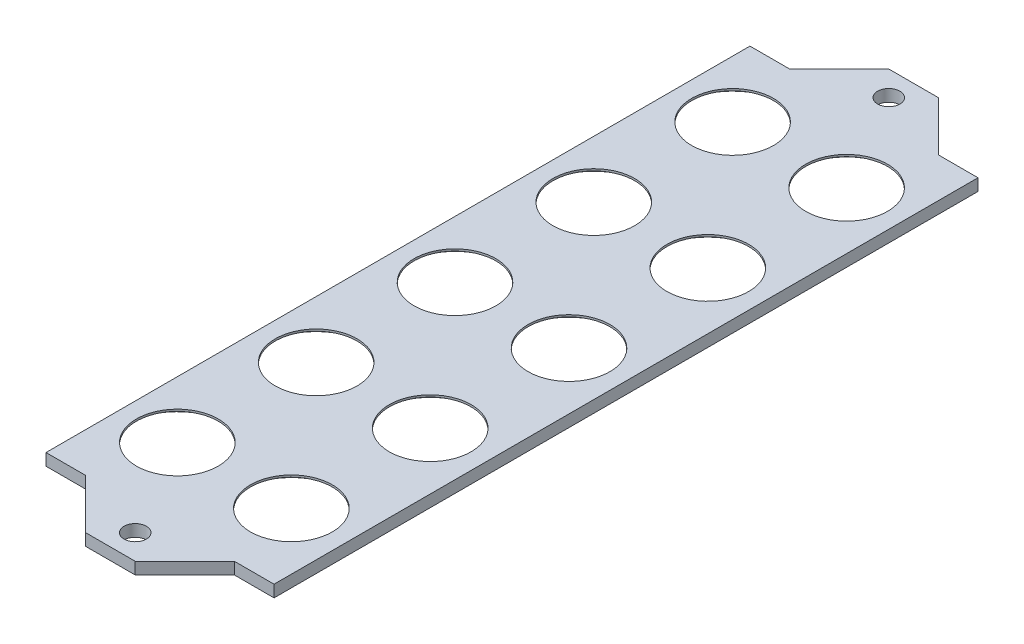
SolidWorks part; units mm, degrees
ref_plane "Front Plane" through (0, 0, 0) normal (0, 0, 1) x (1, 0, 0)
ref_plane "Top Plane" through (0, 0, 0) normal (0, 1, 0) x (1, 0, 0)
ref_plane "Right Plane" through (0, 0, 0) normal (1, 0, 0) x (0, 0, -1)
sketch "Szkic1" plane through (0, 0, 0) normal (0, 1, 0) x (1, 0, 0)
  line L0 (6.5, 25) -> (-3.5, 15)
  line L1 (-11.5, 15) -> (34.5, 15)
  line L2 (-11.5, 15) -> (-11.5, -127)
  line L3 (-11.5, -127) -> (34.5, -127)
  line L4 (34.5, 15) -> (34.5, -127)
  line L5 (6.5, 15) -> (16.5, 15)
  line L6 (6.5, 15) -> (6.5, 25)
  line L7 (6.5, 25) -> (16.5, 25)
  line L8 (16.5, 15) -> (16.5, 25)
  line L9 (16.5, 25) -> (26.5, 15)
  line L12 (-11.5, -56) -> (-33.554, -56) construction
  line L13 (16.5, -137) -> (26.5, -127)
  line L14 (16.5, -127) -> (16.5, -137)
  line L15 (6.5, -127) -> (6.5, -137)
  line L16 (6.5, -137) -> (16.5, -137)
  line L17 (6.5, -137) -> (-3.5, -127)
  line L18 (-11.5, -155) -> (34.5, -155) [skipped]
  line L19 (-11.5, -183) -> (34.5, -183) [skipped]
  circle A0 centre (0, 0) radius 8.25
  circle A1 centre (0, 0) radius 10.6
  circle A2 centre (0, 0) radius 10.1
  circle A3 centre (0, 0) radius 11
  circle A5 centre (23, 0) radius 8.25
  circle A6 centre (23, 0) radius 10.6
  circle A7 centre (23, 0) radius 10.1
  circle A8 centre (23, 0) radius 11
  circle A10 centre (23, -28) radius 8.25
  circle A11 centre (23, -28) radius 10.6
  circle A12 centre (23, -28) radius 10.1
  circle A13 centre (23, -28) radius 11
  circle A15 centre (0, -28) radius 8.25
  circle A16 centre (0, -28) radius 10.6
  circle A17 centre (0, -28) radius 10.1
  circle A18 centre (0, -28) radius 11
  circle A20 centre (0, -56) radius 11
  circle A21 centre (0, -56) radius 10.6
  circle A22 centre (0, -56) radius 10.1
  circle A23 centre (0, -56) radius 8.25
  circle A24 centre (23, -56) radius 8.25
  circle A25 centre (23, -56) radius 10.1
  circle A26 centre (23, -56) radius 10.6
  circle A27 centre (23, -56) radius 11
  circle A28 centre (0, -84) radius 11
  circle A29 centre (0, -84) radius 10.6
  circle A30 centre (0, -84) radius 10.1
  circle A31 centre (0, -84) radius 8.25
  circle A32 centre (23, -84) radius 8.25
  circle A33 centre (23, -84) radius 10.1
  circle A34 centre (23, -84) radius 10.6
  circle A35 centre (23, -84) radius 11
  circle A36 centre (0, -112) radius 11
  circle A37 centre (0, -112) radius 10.6
  circle A38 centre (0, -112) radius 10.1
  circle A39 centre (0, -112) radius 8.25
  circle A40 centre (23, -112) radius 8.25
  circle A41 centre (23, -112) radius 10.1
  circle A42 centre (23, -112) radius 10.6
  circle A43 centre (23, -112) radius 11
  dimension "D1" = 16.5
  dimension "D2" = 20.2
  dimension "D3" = 21.2
  dimension "D4" = 0.4
  dimension "D5" = 23
  dimension "D8" = 11.5
  dimension "D10" = 2
  dimension "D9" = 11.5
  dimension "D11" = 15
  dimension "D12" = 10
  dimension "D13" = 18
  dimension "D14" = 10
  dimension "D15" = 3
  dimension "D16" = 15
  dimension "D17" = 45
  dimension "D18" = 45
  dimension "D6" = 2
  dimension "D7" = 2
extrude "Dodanie-wyciągnięcie1" add sketch "Szkic1" along normal blind 0.4 contours L4 L1 L2 | L4 L2 | L2 L3 L4 | A18 | A18 A16 | A16 A17 | A17 A15 | A12 A10 | A11 A12 | A13 A11 | A13 | A7 A5 | A6 A7 | A8 A6 | A8 | A3 | A3 A1 | A1 A2 | A2 A0 | L1 L6 L0 | L1 L8 L7 L6 | L9 L8 L1 | A22 A23 | A21 A22 | A20 A21 | A25 A24 | A26 A25 | A27 A26 | A33 A32 | A34 A33 | A35 A34 | A28 A29 | A29 A30 | A30 A31 | A41 A40 | A42 A41 | A43 A42 | A38 A39 | A37 A38 | A36 A37 | L15 L16 L14 L3 | L17 L15 L3 | L3 L14 L13 region at (3.1667, 0, -18.3333) region at (11.5, 0, -20) region at (11.5, 0, 56) region at (19.8333, 0, -18.3333) region at (3.1667, 0, 130.3333) region at (11.5, 0, 132) region at (19.8333, 0, 130.3333) region at (-10.3002, 0, 0) region at (-9.8143, 0, 0) region at (-10.6889, 0, 0) region at (12.6998, 0, 0) region at (13.1857, 0, 0) region at (12.3111, 0, 0) region at (12.6998, 0, 28) region at (13.1857, 0, 28) region at (12.3111, 0, 28) region at (-10.3002, 0, 28) region at (-9.8143, 0, 28) region at (-10.6889, 0, 28) region at (-10.6889, 0, 56) region at (-10.3002, 0, 56) region at (-9.8143, 0, 56) region at (13.1857, 0, 56) region at (12.6998, 0, 56) region at (12.3111, 0, 56) region at (-10.6889, 0, 84) region at (-10.3002, 0, 84) region at (-9.8143, 0, 84) region at (13.1857, 0, 84) region at (12.6998, 0, 84) region at (12.3111, 0, 84) region at (-10.6889, 0, 112) region at (-10.3002, 0, 112) region at (-9.8143, 0, 112) region at (13.1857, 0, 112) region at (12.6998, 0, 112) region at (12.3111, 0, 112)
extrude "Dodanie-wyciągnięcie2" add sketch "Szkic1<3>" against normal blind 2 from surface contours A3 | A8 | L4 L1 L2 | L4 L2 | A18 | A13 | L2 L3 L4 | L1 L6 L0 | L1 L8 L7 L6 | L9 L8 L1 | L17 L15 L3 | L15 L16 L14 L3 | L3 L14 L13 region at (3.1667, 0, -18.3333) region at (11.5, 0, -20) region at (11.5, 0, 56) region at (19.8333, 0, -18.3333) region at (3.1667, 0, 130.3333) region at (11.5, 0, 132) region at (19.8333, 0, 130.3333) starting at face at (11.5, 0, 56)
sketch "Szkic1<3>" plane through (0, 0, 0) normal (0, 1, 0) x (1, 0, 0) same geometry as "Szkic1"
sketch "Szkic2" plane through (0, 0.4, 0) normal (0, 1, 0) x (1, 0, 0)
  line L0 (-11.5, 15) -> (34.5, 15)
  line L1 (11.5, 15) -> (11.5, 25)
  line L2 (6.5, 25) -> (16.5, 25) construction
  line L3 (-11.5, -56) -> (34.5, -56) construction
  line L4 (-11.5, 15) -> (-11.5, -127) construction
  line L5 (34.5, 15) -> (34.5, -127) construction
  circle A0 centre (11.5, 20) radius 2.25
  circle A1 centre (11.5, -132) radius 2.25
  dimension "D1" = 4.5
extrude "Wytnij-wyciągnięcie1" cut sketch "Szkic2" against normal blind 20 contours L1 A0 | L1 A0 | A1 region at (10.5451, 0.4, -20) region at (12.4549, 0.4, -20) region at (11.5, 0.4, 132)
